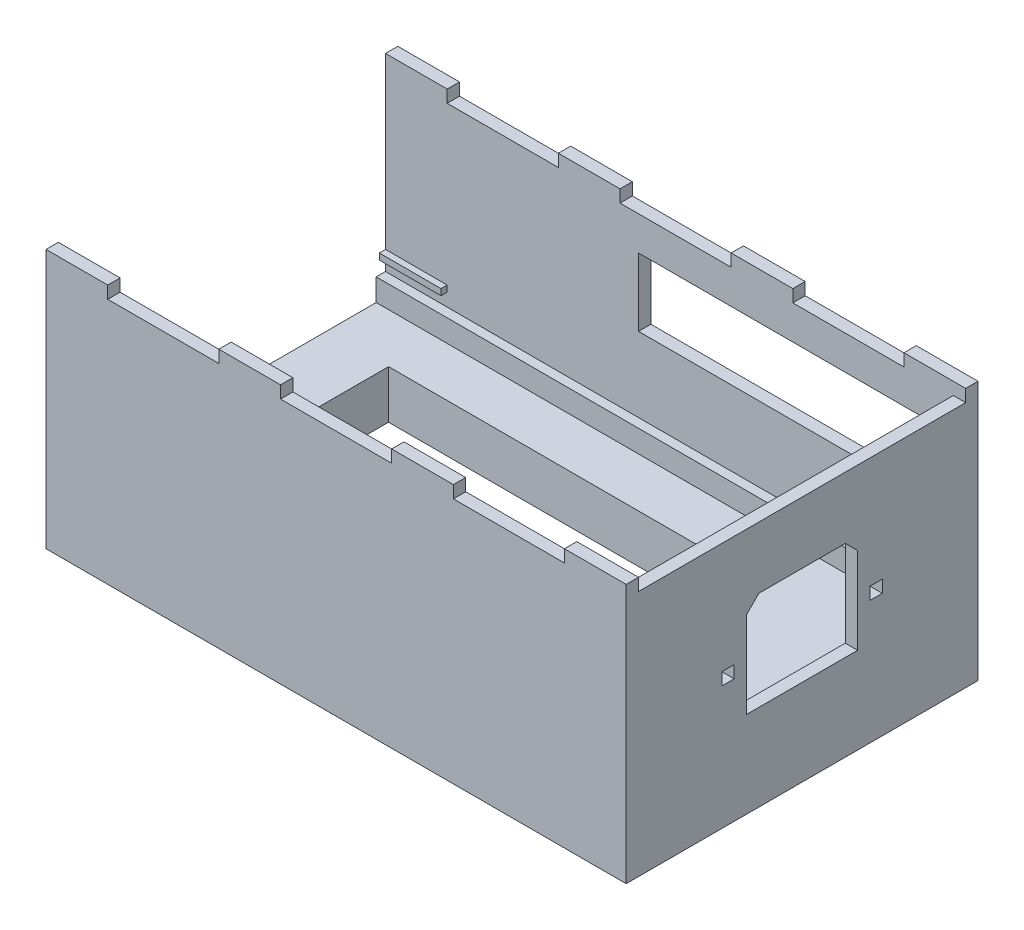
SolidWorks part; units mm, degrees
ref_plane "Front Plane" through (0, 0, 0) normal (0, 0, 1) x (1, 0, 0)
ref_plane "Top Plane" through (0, 0, 0) normal (0, 1, 0) x (1, 0, 0)
ref_plane "Right Plane" through (0, 0, 0) normal (1, 0, 0) x (0, 0, -1)
sketch "Sketch1" plane through (0, 0, 0) normal (0, 1, 0) x (1, 0, 0)
  line L1 (-30.298, 32.6459) -> (63.702, 32.6459)
  line L2 (-30.298, 32.6459) -> (-30.298, -24.3541)
  line L3 (-30.298, -24.3541) -> (63.702, -24.3541)
  line L4 (63.702, 32.6459) -> (63.702, -24.3541)
  dimension "D1" = 94
  dimension "D2" = 57
extrude "Boss-Extrude1" add sketch "Sketch1" along normal blind 10
sketch "Sketch2" plane through (0, 10, 0) normal (0, 1, 0) x (1, 0, 0)
  line L0 (-30.298, 32.6459) -> (63.702, 32.6459)
  line L1 (63.702, 32.6459) -> (63.702, -24.3541)
  line L2 (63.702, -24.3541) -> (-30.298, -24.3541)
  line L3 (-30.298, -24.3541) -> (-30.298, -22.3541)
  line L4 (-30.298, 32.6459) -> (-30.298, -24.3541) construction
  line L5 (-30.298, -22.3541) -> (61.702, -22.3541)
  line L6 (61.702, -22.3541) -> (61.702, 30.6459)
  line L7 (61.702, 30.6459) -> (-30.298, 30.6459)
  line L8 (-30.298, 30.6459) -> (-30.298, 32.6459)
  dimension "D1" = 2
  dimension "D2" = 2
  dimension "D3" = 2
extrude "Boss-Extrude2" add sketch "Sketch2" along normal blind 30
sketch "Sketch3" plane through (-30.298, 0, 0) normal (-1, 0, 0) x (0, 0, 1)
  line L0 (-30.6459, 40) -> (-30.6459, 10) construction
  line L1 (-30.6459, 10) -> (-29.1459, 10)
  line L2 (-30.6459, 10) -> (-30.6459, 11.4)
  line L3 (-30.6459, 11.4) -> (-29.1459, 11.4)
  line L4 (-29.1459, 10) -> (-29.1459, 11.4)
  line L5 (22.3541, 10) -> (20.8541, 10)
  line L6 (22.3541, 10) -> (22.3541, 11.4)
  line L7 (22.3541, 11.4) -> (20.8541, 11.4)
  line L8 (20.8541, 10) -> (20.8541, 11.4)
  line L9 (-30.6459, 14.5) -> (-29.6459, 14.5)
  line L10 (-30.6459, 14.5) -> (-30.6459, 13.5)
  line L11 (-30.6459, 13.5) -> (-29.6459, 13.5)
  line L12 (-29.6459, 14.5) -> (-29.6459, 13.5)
  line L13 (22.3541, 40) -> (22.3541, 10) construction
  line L14 (22.3541, 13.5) -> (21.3541, 13.5)
  line L15 (22.3541, 13.5) -> (22.3541, 14.5)
  line L16 (22.3541, 14.5) -> (21.3541, 14.5)
  line L17 (21.3541, 13.5) -> (21.3541, 14.5)
  dimension "D1" = 1.5
  dimension "D2" = 1.4
  dimension "D3" = 1.5
  dimension "D4" = 1.4
  dimension "D5" = 2.1
  dimension "D6" = 2.1
  dimension "D8" = 1
  dimension "D9" = 1
  dimension "D10" = 1
  dimension "D11" = 1
extrude "Boss-Extrude3" add sketch "Sketch3" against normal up to surface (92 mm away) contours L1 L4 L3 L2 | L5 L8 L7 L6 | L17 L16 L15 L14 up to face at (61.702, 25, -4.1459)
extrude "Boss-Extrude4" add sketch "Sketch3<3>" against normal blind 10 contours L12 L11 L10 L9
sketch "Sketch3<3>" plane through (-30.298, 0, 0) normal (-1, 0, 0) x (0, 0, 1) same geometry as "Sketch3"
sketch "Sketch4" plane through (0, 0, -32.6459) normal (0, 0, -1) x (-1, 0, 0)
  line L0 (-63.702, 40) -> (-63.702, 0) construction
  line L1 (-56.702, 34.5) -> (-10.702, 34.5)
  line L2 (-56.702, 34.5) -> (-56.702, 23.5)
  line L3 (-56.702, 23.5) -> (-10.702, 23.5)
  line L4 (-10.702, 34.5) -> (-10.702, 23.5)
  point P4 (-56.702, 29)
  dimension "D1" = 7
  dimension "D2" = 46
  dimension "D3" = 11
  dimension "D4" = 9
extrude "Cut-Extrude1" cut sketch "Sketch4" against normal blind 10
sketch "Sketch5" plane through (63.702, 0, 0) normal (1, 0, 0) x (0, 0, -1)
  line L0 (-4.8541, 21) -> (13.1459, 21) construction
  line L1 (-2.8541, 30) -> (11.1459, 30)
  line L2 (-4.8541, 28) -> (-4.8541, 14)
  line L3 (-4.8541, 14) -> (13.1459, 14)
  line L4 (13.1459, 28) -> (13.1459, 14)
  line L5 (-24.3541, 40) -> (32.6459, 40) construction
  line L6 (4.1459, 40) -> (4.1459, 0) construction
  line L7 (-4.8541, 21) -> (-24.3541, 21) construction
  line L8 (-24.3541, 0) -> (32.6459, 0) construction
  line L9 (-24.3541, 40) -> (-24.3541, 0) construction
  line L10 (13.1459, 21) -> (32.6459, 21) construction
  line L11 (32.6459, 40) -> (32.6459, 0) construction
  line L12 (11.1459, 30) -> (13.1459, 28)
  line L13 (-8.8541, 22) -> (-6.8541, 22)
  line L14 (-8.8541, 22) -> (-8.8541, 20)
  line L15 (-8.8541, 20) -> (-6.8541, 20)
  line L16 (-6.8541, 22) -> (-6.8541, 20)
  line L17 (15.1459, 22) -> (17.1459, 22)
  line L18 (15.1459, 22) -> (15.1459, 20)
  line L19 (15.1459, 20) -> (17.1459, 20)
  line L20 (17.1459, 22) -> (17.1459, 20)
  line L21 (-4.8541, 28) -> (-2.8541, 30)
  point P10 (4.1459, 30)
  point P27 (-6.8541, 21)
  point P28 (17.1459, 21)
  dimension "D1" = 0
  dimension "D3" = 10
  dimension "D5" = 2
  dimension "D6" = 0
  dimension "D7" = 2
  dimension "D8" = 2
  dimension "D9" = 2
  dimension "D10" = 2
  dimension "D11" = 0
  dimension "D12" = 2
  dimension "D13" = 45
  dimension "D15" = 45
extrude "Cut-Extrude2" cut sketch "Sketch5" against normal up to surface (2 mm away) up to face at (61.702, 16.8, 4.5207)
ref_plane "Plane5" through (0, 33, 0) normal (0, 1, 0) x (1, 0, 0)
sketch "Sketch7" plane through (0, 33, 0) normal (0, 1, 0) x (1, 0, 0)
  line L0 (61.702, -22.3541) -> (-30.298, -22.3541) construction
  line L1 (10.702, -22.3541) -> (61.702, -22.3541)
  line L2 (10.702, -22.3541) -> (10.702, -20.3541)
  line L3 (10.702, -20.3541) -> (59.702, -20.3541)
  line L4 (61.702, -22.3541) -> (61.702, -20.3541)
  line L5 (61.702, 29.1459) -> (61.702, -20.8541) construction
  line L6 (61.702, 30.6459) -> (61.702, -22.3541) construction
  line L8 (59.702, -20.3541) -> (59.702, 15.6459)
  line L9 (59.702, 15.6459) -> (61.702, 15.6459)
  line L10 (61.702, -20.3541) -> (61.702, 15.6459)
  dimension "D1" = 51
  dimension "D2" = 2
  dimension "D3" = 38
  dimension "D4" = 2
extrude "Boss-Extrude5" add sketch "Sketch7" against normal blind 2 contours L3 L8 L9 L10 L4 L1 L2
fillet "Fillet1" radius 1.5 2 edges at (59.702, 31, 2.3541) (35.202, 31, 20.3541) conic radius 3
ref_plane "Plane6" through (0, 34.8, 0) normal (0, 1, 0) x (1, 0, 0)
sketch "Sketch8" plane through (0, 34.8, 0) normal (0, 1, 0) x (1, 0, 0)
  line L1 (10.702, -20.3541) -> (59.702, -20.3541)
  line L2 (10.702, -20.3541) -> (10.702, -22.3541)
  line L3 (10.702, -22.3541) -> (61.702, -22.3541)
  line L4 (61.702, -20.3541) -> (61.702, -22.3541)
  line L5 (61.702, -22.3541) -> (59.702, -22.3541)
  line L6 (61.702, -22.3541) -> (61.702, 15.6459)
  line L7 (61.702, 15.6459) -> (59.702, 15.6459)
  line L8 (59.702, -20.3541) -> (59.702, 15.6459)
extrude "Boss-Extrude6" add sketch "Sketch8" along normal blind 1 contours L6 L7 L8 L1 L2 L3
sketch "Sketch9" plane through (0, 40, 0) normal (0, 1, 0) x (1, 0, 0)
  line L0 (-30.298, 30.6459) -> (61.702, 30.6459) construction
  line L1 (-30.298, 32.6459) -> (-20.298, 32.6459)
  line L2 (-30.298, 32.6459) -> (-30.298, 30.6459)
  line L3 (-30.298, 30.6459) -> (-20.298, 30.6459)
  line L4 (-20.298, 32.6459) -> (-20.298, 30.6459)
  line L5 (61.702, 30.6459) -> (-30.298, 30.6459) construction
  line L6 (-2.298, 30.6459) -> (7.702, 30.6459)
  line L7 (-2.298, 30.6459) -> (-2.298, 32.6459)
  line L8 (-2.298, 32.6459) -> (7.702, 32.6459)
  line L9 (7.702, 30.6459) -> (7.702, 32.6459)
  line L10 (63.702, 32.6459) -> (-30.298, 32.6459) construction
  line L11 (61.702, -22.3541) -> (-30.298, -22.3541) construction
  line L12 (25.702, 30.6459) -> (35.702, 30.6459)
  line L13 (25.702, 30.6459) -> (25.702, 32.6459)
  line L14 (25.702, 32.6459) -> (35.702, 32.6459)
  line L15 (35.702, 30.6459) -> (35.702, 32.6459)
  line L16 (53.702, 30.6459) -> (63.702, 30.6459)
  line L17 (53.702, 30.6459) -> (53.702, 32.6459)
  line L18 (53.702, 32.6459) -> (63.702, 32.6459)
  line L19 (63.702, 30.6459) -> (63.702, 32.6459)
  line L20 (-30.298, -24.3541) -> (-20.298, -24.3541)
  line L21 (-30.298, -24.3541) -> (-30.298, -22.3541)
  line L22 (-30.298, -22.3541) -> (-20.298, -22.3541)
  line L23 (-20.298, -24.3541) -> (-20.298, -22.3541)
  line L24 (-30.298, -24.3541) -> (63.702, -24.3541) construction
  line L25 (-2.298, -24.3541) -> (7.702, -24.3541)
  line L26 (-2.298, -24.3541) -> (-2.298, -22.3541)
  line L27 (-2.298, -22.3541) -> (7.702, -22.3541)
  line L28 (7.702, -24.3541) -> (7.702, -22.3541)
  line L29 (10.702, -22.3541) -> (61.702, -22.3541) construction
  line L30 (25.702, -24.3541) -> (35.702, -24.3541)
  line L31 (25.702, -24.3541) -> (25.702, -22.3541)
  line L32 (25.702, -22.3541) -> (35.702, -22.3541)
  line L33 (35.702, -24.3541) -> (35.702, -22.3541)
  line L35 (63.702, -24.3541) -> (53.702, -24.3541)
  line L36 (63.702, -24.3541) -> (63.702, -22.3541)
  line L37 (63.702, -22.3541) -> (53.702, -22.3541)
  line L38 (53.702, -24.3541) -> (53.702, -22.3541)
  dimension "D1" = 10
  dimension "D2" = 10
  dimension "D3" = 18
  dimension "D4" = 18
  dimension "D5" = 10
  dimension "D6" = 18
  dimension "D7" = 18
  dimension "D8" = 18
  dimension "D9" = 18
  dimension "D10" = 10
  dimension "D11" = 10
  dimension "D12" = 10
extrude "Boss-Extrude7" add sketch "Sketch9" along normal blind 2
sketch "Sketch10" plane through (0, 10, 0) normal (0, 1, 0) x (1, 0, 0)
  line L0 (-30.298, 4.1459) -> (61.702, 4.1459) construction
  line L1 (-20.298, 21.1459) -> (31.702, 21.1459)
  line L2 (-20.298, 21.1459) -> (-20.298, -12.8541)
  line L3 (-20.298, -12.8541) -> (31.702, -12.8541)
  line L4 (31.702, 21.1459) -> (31.702, -12.8541)
  line L5 (-30.298, 29.1459) -> (-30.298, -20.8541) construction
  line L6 (61.702, 30.6459) -> (61.702, -22.3541) construction
  point P10 (31.702, 4.1459)
  dimension "D1" = 34
  dimension "D2" = 0
  dimension "D3" = 52
  dimension "D4" = 10
extrude "Cut-Extrude3" cut sketch "Sketch10" against normal through all and the other way through all
sketch "Sketch11" plane through (0, 10, 0) normal (0, 1, 0) x (1, 0, 0)
  line L1 (61.702, 29.1459) -> (-30.298, 29.1459)
  line L2 (61.702, 29.1459) -> (61.702, -20.8541)
  line L3 (61.702, -20.8541) -> (-30.298, -20.8541)
  line L4 (-30.298, 29.1459) -> (-30.298, -20.8541)
extrude "Cut-Extrude4" cut sketch "Sketch11" against normal blind 2.2
sketch "Sketch12" plane through (63.702, 0, 0) normal (1, 0, 0) x (0, 0, -1)
  line L0 (17.1459, 20) -> (17.1459, 22) construction
  line L1 (-8.8541, 30) -> (17.1459, 30)
  line L2 (-8.8541, 30) -> (-8.8541, 14)
  line L3 (-8.8541, 14) -> (17.1459, 14)
  line L4 (17.1459, 30) -> (17.1459, 14)
  line L5 (-8.8541, 22) -> (-8.8541, 20) construction
  line L6 (-4.8541, 14) -> (13.1459, 14) construction
  line L7 (11.1459, 30) -> (-2.8541, 30) construction
  line L8 (15.1459, 20) -> (17.1459, 20) construction
  line L9 (-4.8541, 14) -> (-4.8541, 30) construction
  line L10 (13.1459, 14) -> (13.1459, 30) construction
  line L11 (-6.8541, 20) -> (-6.8541, 22) construction
  dimension "D1" = 0
  dimension "D2" = 0
  dimension "D3" = 0
  dimension "D4" = 0
  dimension "D5" = 2
  dimension "D6" = 16
  dimension "D7" = 16
  dimension "D8" = 26
  dimension "D9" = 18
  dimension "D10" = 16
  dimension "D11" = 6
